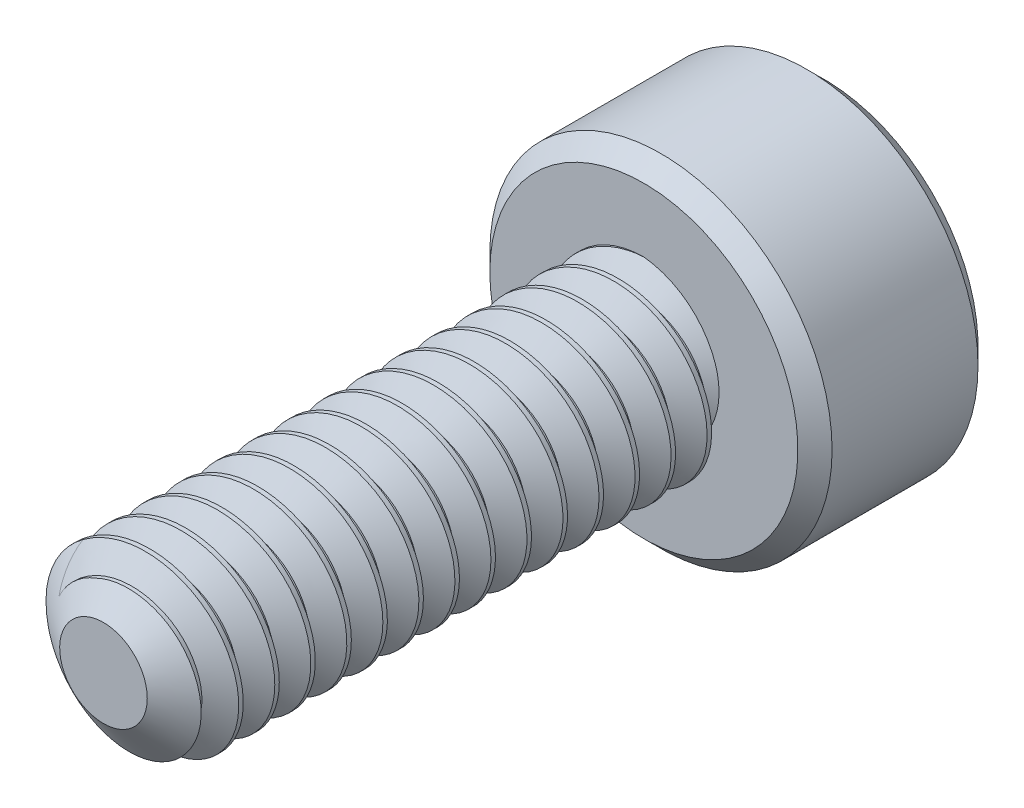
SolidWorks part; units mm, degrees
ref_plane "Front Plane" through (0, 0, 0) normal (0, 0, 1) x (1, 0, 0)
ref_plane "Top Plane" through (0, 0, 0) normal (0, 1, 0) x (1, 0, 0)
ref_plane "Right Plane" through (0, 0, 0) normal (1, 0, 0) x (0, 0, -1)
sketch "Shaft Sketch" plane through (0, 0, 0) normal (0, 0, 1) x (1, 0, 0)
  circle A0 centre (0, 0) radius 1
  dimension "OD" = 2
extrude "Shaft Extrude" add sketch "Shaft Sketch" against normal blind 6
sketch "Thread Spiral Sketch" plane through (0, 0, 0) normal (0, 0, 1) x (1, 0, 0)
  circle A0 centre (0, 0) radius 1 construction
  circle A1 centre (0, 0) radius 1
curve "Thread Helix/Spiral" pitch 0.4 height 6.4 radius 1 centre (0, 0, 0) axis (0, 0, -1) start towards (0, 1, 0) parameters "pitch"=0.4
sketch "Thread Cut Sketch" plane through (0, 0, 0) normal (1, 0, 0) x (0, 0, -1)
  line L0 (-0.35, 1) -> (-0.2, 0.7402)
  line L1 (-0.2, 0.7402) -> (-0.15, 0.7402)
  line L2 (-0.15, 0.7402) -> (0, 1)
  line L3 (-0.35, 1) -> (0, 1)
  line L4 (-0.175, 1) -> (-0.175, 0.7402) construction
  line L5 (-0.275, 0.8701) -> (-0.075, 0.8701) construction
  line L6 (0, 1) -> (0, -1) construction
  dimension "D1" = 0.05
  dimension "D2" = 0.2
  dimension "D3" = 60
sweep "Thread Cut Sweep" cut profiles "Thread Cut Sketch" path "Thread Helix/Spiral" align with end faces yes
sketch "End Chamfer Sketch" plane through (0, 0, 0) normal (1, 0, 0) x (0, 0, -1)
  line L0 (0.3598, 1) -> (0, 0.4862)
  line L1 (0, 0.4862) -> (0, 1)
  line L2 (0.3598, 1) -> (0, 1)
  line L3 (-0.35, 1) -> (0, 1) construction
  line L4 (0, 0) -> (7.0209, 0) construction
  dimension "D1" = 55
  dimension "D2" = 0.254
revolve "End Chamfer Revolve" cut sketch "End Chamfer Sketch" angle 360 about L4
sketch "Head Extrude Sketch" plane through (0, 0, -6) normal (0, 0, -1) x (-1, 0, 0)
  circle A0 centre (0, 0) radius 1.9
  dimension "head dia" = 3.8
extrude "Head Extrude" add sketch "Head Extrude Sketch" along normal blind 2
sketch "Sketch7" plane through (0, 0, -8) normal (0, 0, -1) x (-1, 0, 0)
  line L1 (0, 0.866) -> (-0.75, 0.433)
  line L2 (-0.75, 0.433) -> (-0.75, -0.433)
  line L3 (-0.75, -0.433) -> (0, -0.866)
  line L4 (0, -0.866) -> (0.75, -0.433)
  line L5 (0.75, -0.433) -> (0.75, 0.433)
  line L6 (0.75, 0.433) -> (0, 0.866)
  circle A0 centre (0, 0) radius 0.75 construction
  dimension "hex dia" = 1.5
extrude "Socket Cut Extrude" cut sketch "Sketch7" against normal blind 1.125
sketch "Socket Entry Sketch" plane through (0, 0, -8) normal (0, 0, -1) x (-1, 0, 0)
  circle A0 centre (0, 0) radius 0.866
extrude "Socket Entry Cut Extrude" cut sketch "Socket Entry Sketch" against normal through all draft 45
chamfer "Head Chamfer" distance 0.19 angle 45 2 edges at (-1.9, 0, -8) (-1.9, 0, -6)
sketch "Sketch10" plane through (0, 0, -6) normal (0, 0, 1) x (1, 0, 0)
  circle A1 centre (0, 0) radius 1
  circle A2 centre (0, 0) radius 1
  dimension "D1" = 0
ref_plane "Partial Thread Plane" through (0, 0, -17) normal (0, 0, 1) x (1, 0, 0)
extrude "Partial Thread Extrude" [suppressed] add sketch "Sketch10" along normal up to surface (1 mm away) separate body up to plane "Partial Thread Plane"
chamfer "Partial Thread Chamfer" [suppressed] distance 0.04 angle 45
combine bodies "Partial Thread Combine" [suppressed] operation type add bodies to combine 107 108
equation "\"D3@Thread Helix/Spiral\" = \"screw length@Shaft Extrude\" + \"pitch@Thread Helix/Spiral\""
equation "\"D1@Thread Cut Sketch\" = \"pitch@Thread Helix/Spiral\" * .125"
equation "\"D2@Thread Cut Sketch\" = \"pitch@Thread Helix/Spiral\" * .5"
equation "\"D1@Socket Cut Extrude\" = \"hex dia@Sketch7\" * .75"
equation "\"D1@Head Chamfer\" = \"head dia@Head Extrude Sketch\" * .05"
equation "\"D1@Partial Thread Chamfer\" = \"OD@Shaft Sketch\" * .02"
equation "\"Screw Diameter\"= 2mm"
equation "\"Thread Pitch\" = 0.4mm"
equation "\"Head Height\"= 2mm"
equation "\"Hex Size\"= 1.5mm"
equation "\"Head Diameter\"= 3.8mm"
equation "\"OD@Shaft Sketch\"=\"Screw Diameter\""
equation "\"pitch@Thread Helix/Spiral\"=\"Thread Pitch\""
equation "\"head dia@Head Extrude Sketch\"=\"Head Diameter\""
equation "\"head depth@Head Extrude\"=\"Head Height\""
